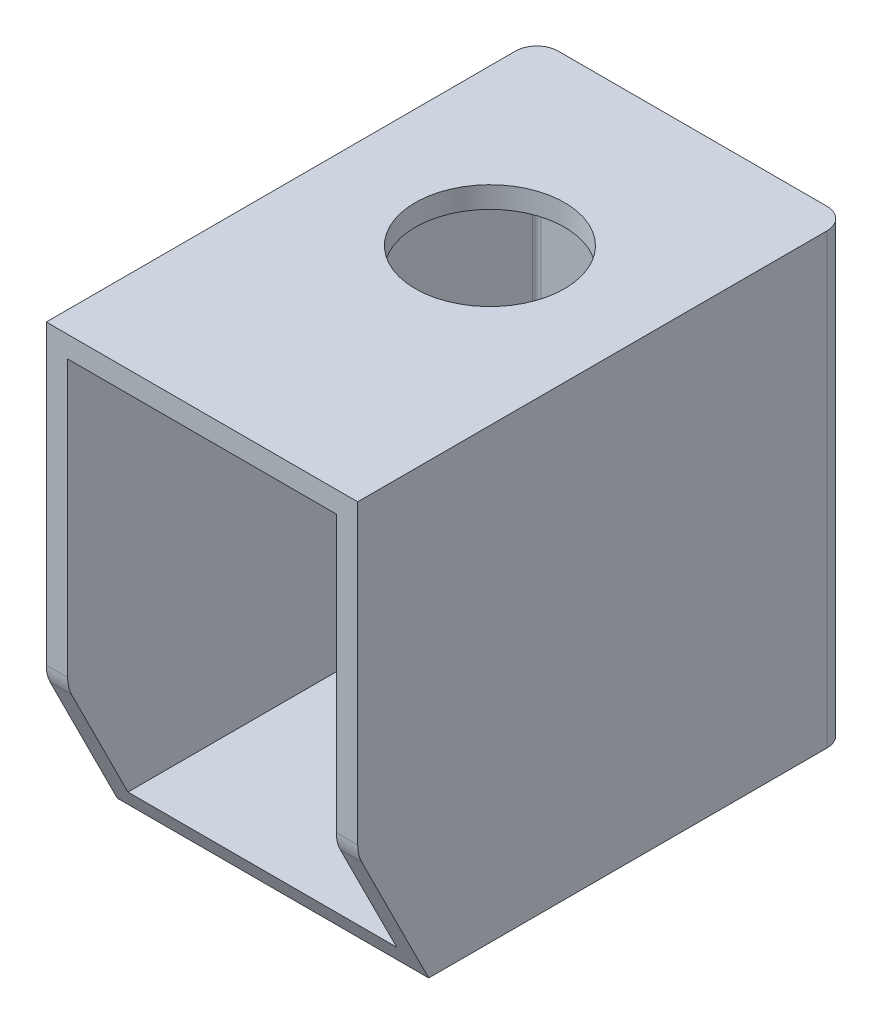
SolidWorks part; units mm, degrees
material "Alloy Steel"
ref_plane "Front Plane" through (0, 0, 0) normal (0, 0, 1) x (1, 0, 0)
ref_plane "Top Plane" through (0, 0, 0) normal (0, 1, 0) x (1, 0, 0)
ref_plane "Right Plane" through (0, 0, 0) normal (1, 0, 0) x (0, 0, -1)
sketch "MainBodyS" plane through (0, 0, 0) normal (0, 1, 0) x (1, 0, 0)
  line L1 (-7.3, 11.5) -> (7.3, 11.5)
  line L2 (-7.3, 11.5) -> (-7.3, -11.5)
  line L3 (-7.3, -11.5) -> (7.3, -11.5)
  line L4 (7.3, 11.5) -> (7.3, -11.5)
  line L5 (-7.3, 11.5) -> (7.3, -11.5) construction
  line L6 (-7.3, -11.5) -> (7.3, 11.5) construction
  point P0 (0, 0)
  dimension "Width" = 14.6
  dimension "Length" = 23
extrude "MAIN BODY" add sketch "MainBodyS" along normal mid plane 21
fillet "MB FILLET" radius 1 2 edges at (-7.3, 0, -11.5) (7.3, 0, -11.5)
shell "SHELL MB" thickness 1 removed face at (0, 0, 11.5)
sketch "TopBoreS" plane through (0, 10.5, 0) normal (0, 1, 0) x (1, 0, 0)
  line L0 (0, 0) -> (0, 2) construction
  line L1 (6.3, 11.5) -> (-6.3, 11.5) construction
  circle A0 centre (0, 2) radius 3.5
  dimension "Dia" = 7
  dimension "YLoc" = 9.5
extrude "TOP BORE" cut sketch "TopBoreS" against normal up to next
sketch "BottomBoreS" plane through (0, -9.5, 0) normal (0, 1, 0) x (1, 0, 0)
  circle A0 centre (0, 2) radius 4.1
  circle A1 centre (0, 2) radius 3.5 construction
  dimension "BottomDiaControl" = 0.6
extrude "BOTTOM BORE" cut sketch "BottomBoreS" against normal through all
sketch "AngledCutS" plane through (0, 0, 0) normal (1, 0, 0) x (0, 0, -1)
  line L0 (-11.5, -3.85) -> (-8.17, -10.5)
  line L1 (-11.5, 10.5) -> (-11.5, -10.5) construction
  line L2 (-2.1, -10.5) -> (6.1, -10.5) construction
  dimension "D1" = 6.65
  dimension "D2" = 3.33
extrude "AngledCut" cut sketch "AngledCutS" along normal through all both and the other way through all flip side to cut
fillet "MB INNER FILLET" radius 0.2 2 edges at (6.3, 0, -10.5) (-6.3, 0, -10.5)
fillet "AC F" radius 1.76 2 edges at (6.8, -3.85, 11.5) (-6.8, -3.85, 11.5)
